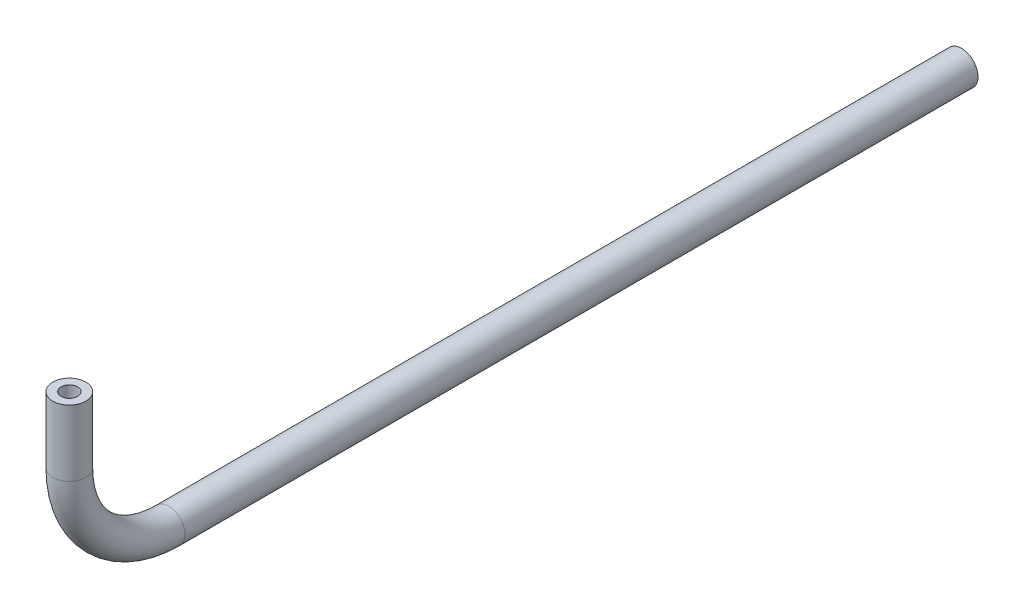
SolidWorks part; units mm, degrees
material "Silicon Rubber"
ref_plane "X-Y Datum" through (0, 0, 0) normal (0, 0, 1) x (1, 0, 0)
ref_plane "X-Z Datum" through (0, 0, 0) normal (0, 1, 0) x (1, 0, 0)
ref_plane "Y-Z Datum" through (0, 0, 0) normal (1, 0, 0) x (0, 0, -1)
sketch3d "3DSketch1"
  line L0 (0, 76.2, 340.36) -> (0, 76.2, 22.86) construction
  line L1 (0, 50.8, 340.36) -> (0, 76.2, 340.36)
  line L2 (0, 12.7, 302.26) -> (0, 12.7, -2.54)
  arc A0 (0, 12.7, 302.26) -> (0, 50.8, 340.36) centre (0, 50.8, 302.26) ccw
  point P4 (-38.1, 50.8, 302.26)
  dimension "D2" = 38.1
  dimension "D4" = 304.8
  dimension "D1" = 317.5
  dimension "D3" = 25.4
sweep "Sweep1" add path "3DSketch1" circular profile diameter 12.7 parameters "D3"=12.7
sweep "Cut-Sweep1" cut path "3DSketch1<3>" circular profile diameter 6.35 parameters "D3"=6.35
sketch3d "3DSketch1<3>" same geometry as "3DSketch1"
